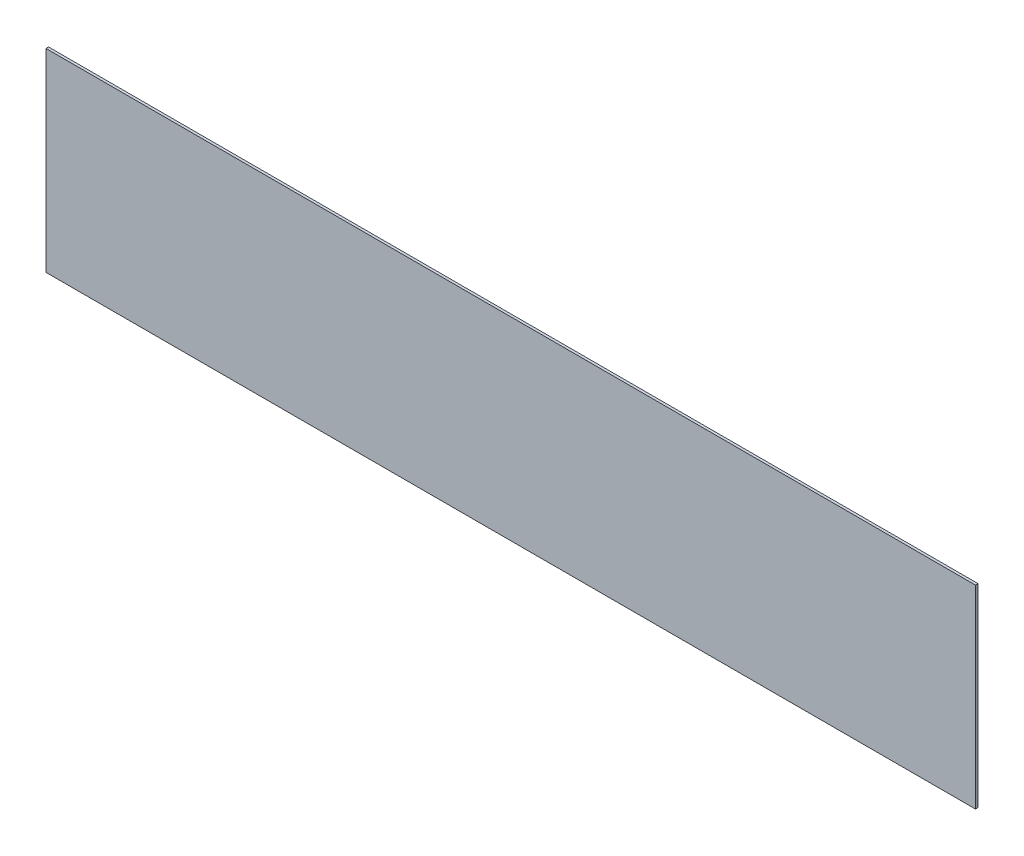
SolidWorks part; units mm, degrees
ref_plane "Front Plane" through (0, 0, 0) normal (0, 0, 1) x (1, 0, 0)
ref_plane "Top Plane" through (0, 0, 0) normal (0, 1, 0) x (1, 0, 0)
ref_plane "Right Plane" through (0, 0, 0) normal (1, 0, 0) x (0, 0, -1)
sketch "Sketch1" plane through (0, 0, 0) normal (0, 0, 1) x (1, 0, 0)
  line L1 (287.5, -60) -> (-287.5, -60)
  line L2 (287.5, -60) -> (287.5, 60)
  line L3 (287.5, 60) -> (-287.5, 60)
  line L4 (-287.5, -60) -> (-287.5, 60)
  line L5 (287.5, -60) -> (-287.5, 60) construction
  line L6 (287.5, 60) -> (-287.5, -60) construction
  point P0 (0, 0)
  dimension "D1" = 120
  dimension "D2" = 575
extrude "Boss-Extrude1" add sketch "Sketch1" along normal blind 1.5875
